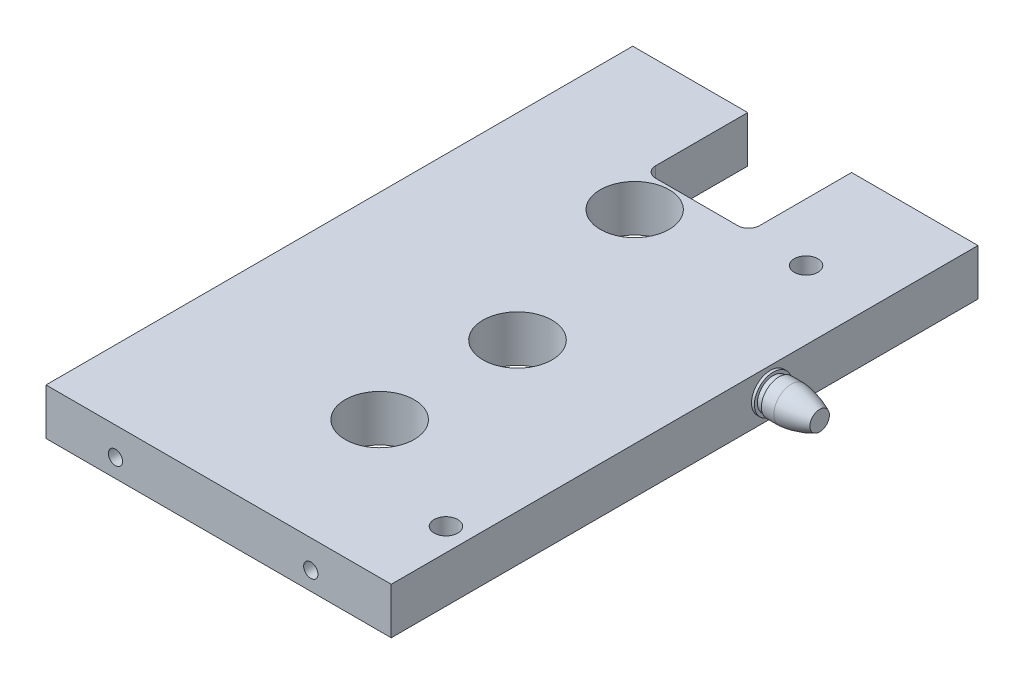
SolidWorks part; units mm, degrees
material "1060 Alloy"
ref_plane "Front Plane" through (0, 0, 0) normal (0, 0, 1) x (1, 0, 0)
ref_plane "Top Plane" through (0, 0, 0) normal (0, 1, 0) x (1, 0, 0)
ref_plane "Right Plane" through (0, 0, 0) normal (1, 0, 0) x (0, 0, -1)
sketch "Sketch1" plane through (0, 0, 0) normal (0, 0, 1) x (1, 0, 0)
  line L0 (-234.625, -82.5) -> (-329.875, -82.5) construction
  line L1 (-234.625, -88.9) -> (-329.875, -88.9)
  line L2 (-234.625, -88.9) -> (-234.625, -76.1)
  line L3 (-234.625, -76.1) -> (-329.875, -76.1)
  line L4 (-329.875, -88.9) -> (-329.875, -76.1)
  line L7 (-329.875, -610.1) -> (-329.875, -622.9) construction
  line L8 (-234.625, -610.1) -> (-234.625, -622.9) construction
  circle A0 centre (-308, -82.5) radius 3.1
  circle A1 centre (-320.5, -82.5) radius 2.395
  circle A2 centre (-244.2, -82.5) radius 2.395
  circle A3 centre (-257.2, -82.5) radius 3.1
  circle A9 centre (-308, -82.5) radius 3.1 construction
  circle A10 centre (-257.2, -82.5) radius 3.1 construction
  circle A11 centre (-244.2, -82.5) radius 3.425 construction
  circle A12 centre (-320.5, -82.5) radius 3.425 construction
  circle A13 centre (-320.5, -616.5) radius 2.395 construction
extrude "Boss-Extrude1" add sketch "Sketch1" along normal up to surface (161.88 mm away) contours L3 L4 L1 L2
extrude "Cut-Extrude1" cut sketch "Sketch1<3>" along normal up to surface (20.2 mm away) contours A0 L0 | A3 L0 | L0 A0 | L0 A3 region at (-257.2, -83.8157, 0) region at (-257.2, -81.1843, 0) region at (-308, -83.8157, 0) region at (-308, -81.1843, 0)
sketch "Sketch1<3>" plane through (0, 0, 0) normal (0, 0, 1) x (1, 0, 0) same geometry as "Sketch1"
extrude "Cut-Extrude2" cut sketch "Sketch1<4>" along normal up to surface (21.5 mm away) contours L0 A2 | A2 L0 | L0 A1 | A1 L0 region at (-244.2, -83.5165, 0) region at (-244.2, -81.4835, 0) region at (-320.5, -81.4835, 0) region at (-320.5, -83.5165, 0)
sketch "Sketch1<4>" plane through (0, 0, 0) normal (0, 0, 1) x (1, 0, 0) same geometry as "Sketch1"
sketch "Sketch2" plane through (0, -76.1, 0) normal (0, 1, 0) x (-1, 0, 0)
  line L3 (269.505, 25.4) -> (269.505, 0)
  line L4 (295.155, 28.4) -> (272.505, 28.4)
  line L5 (298.155, 0) -> (298.155, 25.4)
  line L6 (269.505, 0) -> (298.155, 0)
  line L7 (295.155, 28.4) -> (272.505, 28.4) construction
  line L8 (269.505, 25.4) -> (269.505, 0) construction
  line L9 (298.155, 0) -> (298.155, 25.4) construction
  line L10 (234.625, 0) -> (329.875, 0) construction
  arc A6 (272.505, 28.4) -> (269.505, 25.4) centre (272.505, 25.4) ccw
  arc A7 (298.155, 25.4) -> (295.155, 28.4) centre (295.155, 25.4) ccw
  circle A8 centre (275.57, 86.105) radius 9.525
  circle A9 centre (275.57, 124.135) radius 9.525
  circle A10 centre (253.55, 28.505) radius 3.265
  circle A11 centre (240.925, 140.49) radius 3.265
  arc A12 (272.505, 28.4) -> (269.505, 25.4) centre (272.505, 25.4) ccw construction
  arc A13 (298.155, 25.4) -> (295.155, 28.4) centre (295.155, 25.4) ccw construction
  circle A14 centre (275.57, 86.105) radius 9.525 construction
  circle A15 centre (275.57, 124.135) radius 9.525 construction
  circle A16 centre (240.925, 140.49) radius 3.265 construction
  circle A17 centre (253.55, 28.505) radius 3.265 construction
extrude "Cut-Extrude3" cut sketch "Sketch2" against normal up to next
sketch "Sketch3" plane through (0, -88.9, 0) normal (0, -1, 0) x (1, 0, 0)
  circle A2 centre (-240.925, 140.49) radius 3.265
  circle A3 centre (-253.55, 28.505) radius 9.525
  circle A4 centre (-253.55, 28.505) radius 9.525 construction
  circle A6 centre (-240.925, 140.49) radius 3.265 construction
extrude "Cut-Extrude4" cut sketch "Sketch3" against normal blind 3.32
sketch "Sketch4" plane through (0, 0, 161.88) normal (0, 0, 1) x (1, 0, 0)
  circle A0 centre (-256.825, -83.83) radius 1.965
  circle A1 centre (-310.715, -83.83) radius 1.965
  circle A5 centre (-256.825, -83.83) radius 2.795 construction
  circle A6 centre (-310.715, -83.83) radius 2.795 construction
  dimension "D1" = 3.93
extrude "Cut-Extrude5" cut sketch "Sketch4" against normal up to surface (17.25 mm away)
ref_plane "Plane1" through (0, -82.5, 0) normal (0, 1, 0) x (-1, 0, 0)
sketch "Sketch5" plane through (0, -82.5, 0) normal (0, 1, 0) x (-1, 0, 0)
  line L9 (234.625, 57.29) -> (259.3185, 57.29) construction
  line L10 (234.625, 57.29) -> (221.025, 57.29) construction
  line L11 (221.025, 57.29) -> (221.025, 54.59) construction
  line L12 (232.2758, 52.475) -> (228.8458, 52.475) construction
  line L13 (232.295, 52.925) -> (232.2758, 52.475) construction
  line L14 (233.835, 52.925) -> (232.295, 52.925) construction
  line L15 (233.835, 52.09) -> (233.835, 52.925) construction
  line L16 (234.625, 52.09) -> (233.835, 52.09) construction
  line L17 (234.625, 57.29) -> (234.625, 52.09) construction
  line L18 (234.625, 57.29) -> (259.3185, 57.29) construction
  line L19 (234.625, 57.29) -> (221.025, 57.29)
  line L20 (221.025, 57.29) -> (221.025, 54.59)
  line L21 (232.2758, 52.475) -> (228.8458, 52.475)
  line L22 (232.295, 52.925) -> (232.2758, 52.475)
  line L23 (233.835, 52.925) -> (232.295, 52.925)
  line L24 (233.835, 52.09) -> (233.835, 52.925)
  line L25 (234.625, 52.09) -> (233.835, 52.09)
  line L26 (234.625, 57.29) -> (234.625, 52.09)
  arc A1 (221.025, 54.59) -> (228.8458, 52.475) centre (230.8458, 75.3879) ccw construction
  arc A2 (221.025, 54.59) -> (228.8458, 52.475) centre (230.8458, 75.3879) ccw
revolve "Revolve1" add sketch "Sketch5" angle 360 about L18
sketch "Sketch6" plane through (0, -76.1, 0) normal (0, 1, 0) x (-1, 0, 0)
  circle A0 centre (290.57, 38.77) radius 9.5
  circle A1 centre (290.57, 38.77) radius 3 construction
  dimension "D1" = 19
extrude "Cut-Extrude6" cut sketch "Sketch6" against normal through all
